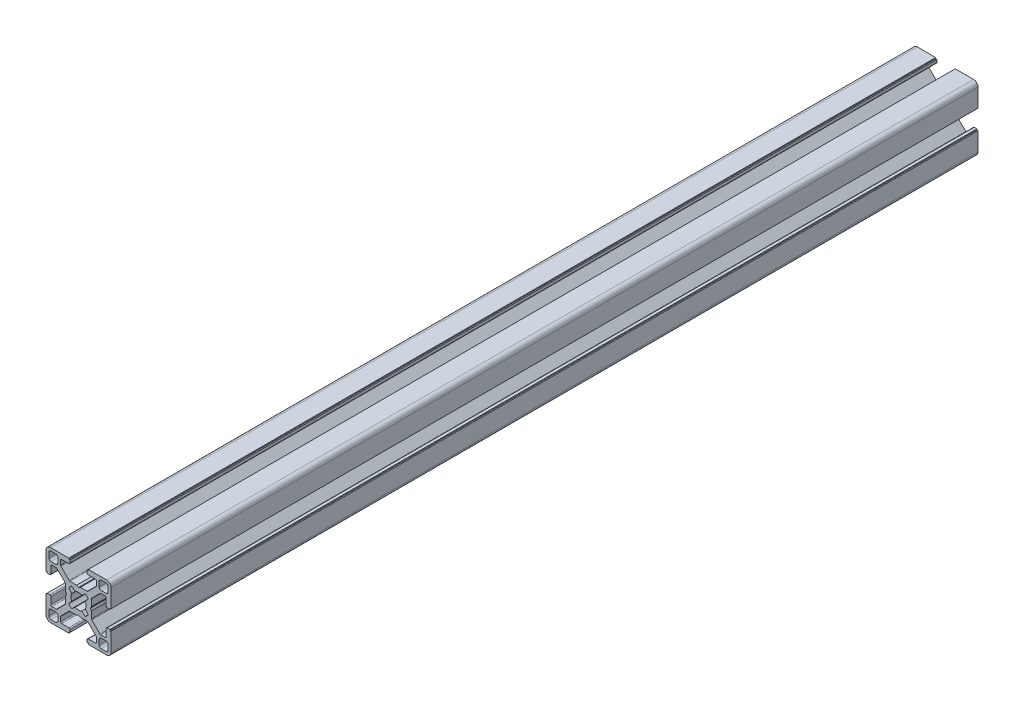
SolidWorks part; units mm, degrees
ref_plane "Front Plane" through (0, 0, 0) normal (0, 0, 1) x (1, 0, 0)
ref_plane "Top Plane" through (0, 0, 0) normal (0, 1, 0) x (1, 0, 0)
ref_plane "Right Plane" through (0, 0, 0) normal (1, 0, 0) x (0, 0, -1)
sketch "Sketch1" plane through (0, 0, 0) normal (0, 0, 1) x (1, 0, 0)
  line L0 (-15, 0) -> (15, 0) construction
  line L1 (0, -15) -> (0, 15) construction
  line L2 (-4.5, 15) -> (4.5, 15) construction
  line L3 (-4, -15) -> (4, -15) construction
  line L4 (-4.5, 15) -> (-4.5, 14.5)
  line L5 (-4.5, 14.5) -> (-4, 14.5)
  line L6 (-4, 14.5) -> (-4, 13.29)
  line L7 (-4.5, 12.79) -> (-7.7675, 12.79)
  line L8 (-8.2675, 12.29) -> (-8.2675, 10.2707)
  line L9 (-8.1211, 9.9171) -> (-4.3504, 6.1464)
  line L10 (-3.9968, 6) -> (0, 6)
  line L11 (0, 0) -> (-15, 15) construction
  line L12 (-4.5, 15) -> (-12.968, 15)
  line L14 (-12.705, 9.5135) -> (-10.5135, 9.5135)
  line L15 (-13.705, 10.5135) -> (-13.705, 12.705)
  line L16 (-12.705, 13.705) -> (-10.5135, 13.705)
  line L17 (-9.5135, 10.5135) -> (-9.5135, 12.705)
  line L18 (-13.705, 9.5135) -> (-9.5135, 13.705) construction
  line L19 (-13.705, 13.705) -> (-9.5135, 9.5135) construction
  line L20 (-3.1568, 4.5038) -> (-1.5303, 3.1477) construction
  line L21 (-4.5038, 3.1568) -> (-3.1477, 1.5303) construction
  line L22 (-6, 3.9968) -> (-6, 0)
  line L23 (-9.9171, 8.1211) -> (-6.1464, 4.3504)
  line L24 (-15, 4.5) -> (-15, 12.968)
  line L25 (-12.29, 8.2675) -> (-10.2707, 8.2675)
  line L26 (-12.79, 4.5) -> (-12.79, 7.7675)
  line L27 (-14.5, 4) -> (-13.29, 4)
  line L28 (-14.5, 4.5) -> (-14.5, 4)
  line L29 (-15, 4.5) -> (-14.5, 4.5)
  circle A0 centre (0, 0) radius 3.5
  arc A1 (-12.968, 15) -> (-15, 12.968) centre (-12.968, 12.968) ccw
  circle A2 centre (0, 0) radius 5.5 construction
  arc A3 (-10.5135, 9.5135) -> (-9.5135, 10.5135) centre (-10.5135, 10.5135) ccw
  arc A4 (-13.705, 12.705) -> (-12.705, 13.705) centre (-12.705, 12.705) cw
  arc A5 (-10.5135, 13.705) -> (-9.5135, 12.705) centre (-10.5135, 12.705) cw
  arc A6 (-12.705, 9.5135) -> (-13.705, 10.5135) centre (-12.705, 10.5135) cw
  arc A7 (-12.79, 4.5) -> (-13.29, 4) centre (-13.29, 4.5) cw
  arc A8 (-12.29, 8.2675) -> (-12.79, 7.7675) centre (-12.29, 7.7675) ccw
  arc A9 (-9.9171, 8.1211) -> (-10.2707, 8.2675) centre (-10.2707, 7.7675) ccw
  arc A10 (-6, 3.9968) -> (-6.1464, 4.3504) centre (-6.5, 3.9968) ccw
  arc A11 (-4.3504, 6.1464) -> (-3.9968, 6) centre (-3.9968, 6.5) ccw
  arc A12 (-4, 13.29) -> (-4.5, 12.79) centre (-4.5, 13.29) cw
  arc A13 (-7.7675, 12.79) -> (-8.2675, 12.29) centre (-7.7675, 12.29) ccw
  arc A14 (-8.2675, 10.2707) -> (-8.1211, 9.9171) centre (-7.7675, 10.2707) ccw
  point P4 (0, 0)
  point P8 (0, 0)
  point P13 (0, 15)
  point P15 (0, -15)
  point P16 (0, 6)
  point P23 (-11.6092, 11.6093)
  point P26 (0, 6)
  point P62 (-12.79, 4)
  point P65 (-12.79, 8.2675)
  point P68 (-10.0636, 8.2675)
  point P71 (-6, 4.2039)
  point P74 (-4.2039, 6)
  point P77 (-4, 12.79)
  point P80 (-8.2675, 12.79)
  point P83 (-8.2675, 10.0636)
  dimension "Center Hole Diameter" = 7
  dimension "D11" = 2.032
  dimension "D9" = 11
  dimension "D13" = 1
  dimension "D14" = 0.5
  dimension "Rail Height" = 30
  dimension "Rail Width" = 30
  dimension "T-Slot Width" = 8
  dimension "T-Slot Depth" = 9
  dimension "D1" = 9
  dimension "D2" = 45
  dimension "D3" = 8
  dimension "D4" = 2.21
  dimension "D5" = 16.535
  dimension "D7" = 2.54
  dimension "D6" = 1.295
  dimension "D8" = 1.246
  dimension "D10" = 10.36
  dimension "D12" = 1.905
sketch "Sketch2" plane through (0, 0, 0) normal (1, 0, 0) x (0, 0, -1)
  line L0 (-76.2, 0) -> (76.2, 0) construction
  line L2 (0, -15) -> (0, 15) construction
  line L3 (0, -15) -> (0, 15) construction
  line L4 (-76.2, -15) -> (-76.2, 15) construction
  line L5 (76.2, -15) -> (76.2, 15) construction
  point P0 (-38.7, 0)
  point P3 (0, 0)
  point P4 (38.7, 0)
  point P12 (-76.2, 0)
  point P14 (76.2, 0)
  dimension "Length" = 152.4
  dimension "D1" = 37.5
sketch "Sketch3" plane through (0, 0, 0) normal (0, 0, 1) x (1, 0, 0)
  line L0 (-4.5038, 3.1568) -> (-3.1477, 1.5303)
  line L1 (0, 3.5) -> (0, 5.5)
  line L2 (-5.5, 0) -> (-3.5, 0)
  line L7 (-6, 3.9968) -> (-6, 0) construction
  line L31 (-9.9171, 8.1211) -> (-6.1464, 4.3504) construction
  line L117 (-12.29, 8.2675) -> (-10.2707, 8.2675) construction
  line L118 (-12.79, 4.5) -> (-12.79, 7.7675) construction
  line L157 (-12.705, 9.5135) -> (-10.5135, 9.5135)
  line L158 (-9.5135, 10.5135) -> (-9.5135, 12.705)
  line L163 (-10.5135, 13.705) -> (-12.705, 13.705)
  line L164 (-13.705, 12.705) -> (-13.705, 10.5135)
  line L165 (-12.705, 9.5135) -> (-10.5135, 9.5135)
  line L166 (-9.5135, 10.5135) -> (-9.5135, 12.705)
  line L167 (-10.5135, 13.705) -> (-12.705, 13.705)
  line L168 (-13.705, 12.705) -> (-13.705, 10.5135)
  line L169 (-14.5, 4) -> (-13.29, 4) construction
  line L170 (-14.5, 4.5) -> (-14.5, 4) construction
  line L171 (-15, 4.5) -> (-14.5, 4.5) construction
  line L172 (-15, 4.5) -> (-15, 12.968) construction
  line L173 (-4.5, 15) -> (-12.968, 15) construction
  line L174 (-4.5, 15) -> (-4.5, 14.5) construction
  line L175 (-4.5, 14.5) -> (-4, 14.5) construction
  line L176 (-4, 14.5) -> (-4, 13.29) construction
  line L177 (-4.5, 12.79) -> (-7.7675, 12.79) construction
  line L178 (-8.2675, 12.29) -> (-8.2675, 10.2707) construction
  line L179 (-8.1211, 9.9171) -> (-4.3504, 6.1464) construction
  line L180 (-3.9968, 6) -> (0, 6) construction
  line L181 (-6, 3.9968) -> (-6, 0.866)
  line L182 (-9.9171, 8.1211) -> (-6.1464, 4.3504)
  line L183 (-12.29, 8.2675) -> (-10.2707, 8.2675)
  line L184 (-12.79, 4.5) -> (-12.79, 7.7675)
  line L185 (-14.5, 4) -> (-13.29, 4)
  line L186 (-14.5, 4.5) -> (-14.5, 4)
  line L187 (-15, 4.5) -> (-14.5, 4.5)
  line L188 (-15, 4.5) -> (-15, 12.968)
  line L189 (-4.5, 15) -> (-12.968, 15)
  line L190 (-4.5, 15) -> (-4.5, 14.5)
  line L191 (-4.5, 14.5) -> (-4, 14.5)
  line L192 (-4, 14.5) -> (-4, 13.29)
  line L193 (-4.5, 12.79) -> (-7.7675, 12.79)
  line L194 (-8.2675, 12.29) -> (-8.2675, 10.2707)
  line L195 (-8.1211, 9.9171) -> (-4.3504, 6.1464)
  line L196 (-3.9968, 6) -> (-0.866, 6)
  line L197 (-0.866, 6) -> (0, 5.5)
  line L198 (0, -15) -> (0, 15) construction
  line L199 (0, 0) -> (-15, 15) construction
  line L200 (0, 0) -> (-15, 15) construction
  line L201 (-3.1568, 4.5038) -> (-1.5303, 3.1477) construction
  line L202 (-3.1568, 4.5038) -> (-1.5303, 3.1477)
  line L203 (-6, 0.866) -> (-5.5, 0)
  line L204 (-15, 0) -> (15, 0) construction
  line L205 (-15, 0) -> (15, 0) construction
  line L206 (0, -15) -> (0, 15) construction
  arc A0 (-3.5, 0) -> (-3.1477, 1.5303) centre (0, 0) cw
  arc A10 (-6, 3.9968) -> (-6.1464, 4.3504) centre (-6.5, 3.9968) ccw construction
  circle A16 centre (0, 0) radius 3.5
  arc A18 (0, 3.5) -> (-1.5303, 3.1477) centre (0, 0) ccw
  arc A20 (-9.9171, 8.1211) -> (-10.2707, 8.2675) centre (-10.2707, 7.7675) ccw construction
  arc A22 (-12.29, 8.2675) -> (-12.79, 7.7675) centre (-12.29, 7.7675) ccw construction
  arc A28 (-13.29, 4) -> (-12.79, 4.5) centre (-13.29, 4.5) ccw construction
  arc A29 (-10.5135, 9.5135) -> (-9.5135, 10.5135) centre (-10.5135, 10.5135) ccw
  arc A30 (-9.5135, 12.705) -> (-10.5135, 13.705) centre (-10.5135, 12.705) ccw
  arc A31 (-12.705, 13.705) -> (-13.705, 12.705) centre (-12.705, 12.705) ccw
  arc A32 (-13.705, 10.5135) -> (-12.705, 9.5135) centre (-12.705, 10.5135) ccw
  arc A33 (-10.5135, 9.5135) -> (-9.5135, 10.5135) centre (-10.5135, 10.5135) ccw
  arc A34 (-9.5135, 12.705) -> (-10.5135, 13.705) centre (-10.5135, 12.705) ccw
  arc A35 (-12.705, 13.705) -> (-13.705, 12.705) centre (-12.705, 12.705) ccw
  arc A36 (-13.705, 10.5135) -> (-12.705, 9.5135) centre (-12.705, 10.5135) ccw
  arc A37 (-12.968, 15) -> (-15, 12.968) centre (-12.968, 12.968) ccw construction
  arc A38 (-4.5, 12.79) -> (-4, 13.29) centre (-4.5, 13.29) ccw construction
  arc A39 (-7.7675, 12.79) -> (-8.2675, 12.29) centre (-7.7675, 12.29) ccw construction
  arc A40 (-8.2675, 10.2707) -> (-8.1211, 9.9171) centre (-7.7675, 10.2707) ccw construction
  arc A41 (-4.3504, 6.1464) -> (-3.9968, 6) centre (-3.9968, 6.5) ccw construction
  arc A42 (-6, 3.9968) -> (-6.1464, 4.3504) centre (-6.5, 3.9968) ccw
  arc A43 (-9.9171, 8.1211) -> (-10.2707, 8.2675) centre (-10.2707, 7.7675) ccw
  arc A44 (-12.29, 8.2675) -> (-12.79, 7.7675) centre (-12.29, 7.7675) ccw
  arc A45 (-13.29, 4) -> (-12.79, 4.5) centre (-13.29, 4.5) ccw
  arc A46 (-12.968, 15) -> (-15, 12.968) centre (-12.968, 12.968) ccw
  arc A47 (-4.5, 12.79) -> (-4, 13.29) centre (-4.5, 13.29) ccw
  arc A48 (-7.7675, 12.79) -> (-8.2675, 12.29) centre (-7.7675, 12.29) ccw
  arc A49 (-8.2675, 10.2707) -> (-8.1211, 9.9171) centre (-7.7675, 10.2707) ccw
  arc A50 (-4.3504, 6.1464) -> (-3.9968, 6) centre (-3.9968, 6.5) ccw
  circle A51 centre (0, 0) radius 5.5 construction
  arc A52 (-3.1568, 4.5038) -> (-4.5038, 3.1568) centre (0, 0) ccw
  dimension "D3" = 60
  dimension "D4" = 60
  dimension "D1" = 0
  dimension "D2" = 0
extrude "Boss-Extrude1" add sketch "Sketch3" along normal mid plane 400
pattern_circular "CirPattern1" count 4 over 360 about axis through (0, 0, 76.2) along (0, 0, -1) of "Boss-Extrude1"
ref_plane "Contact Plane1" through (15, 0, 0) normal (1, 0, 0) x (0, 0, -1)
ref_plane "Contact Plane2" through (0, -15, 0) normal (0, 1, 0) x (1, 0, 0)
ref_plane "Contact Plane3" through (-15, 0, 0) normal (1, 0, 0) x (0, 0, -1)
ref_plane "Contact Plane4" through (0, 15, 0) normal (0, 1, 0) x (1, 0, 0)
equation "\"D1@Sketch2\" = \"Rail Height@Sketch1\" * 1.25"
equation "\"D1@Sketch1\"=\"T-Slot Width@Sketch1\"+1mm"
equation "\"D3@Sketch1\"= \"T-Slot Width@Sketch1\""
equation "\"D1@Boss-Extrude1\"=\"Length\""
equation "\"Length\"= 400"
